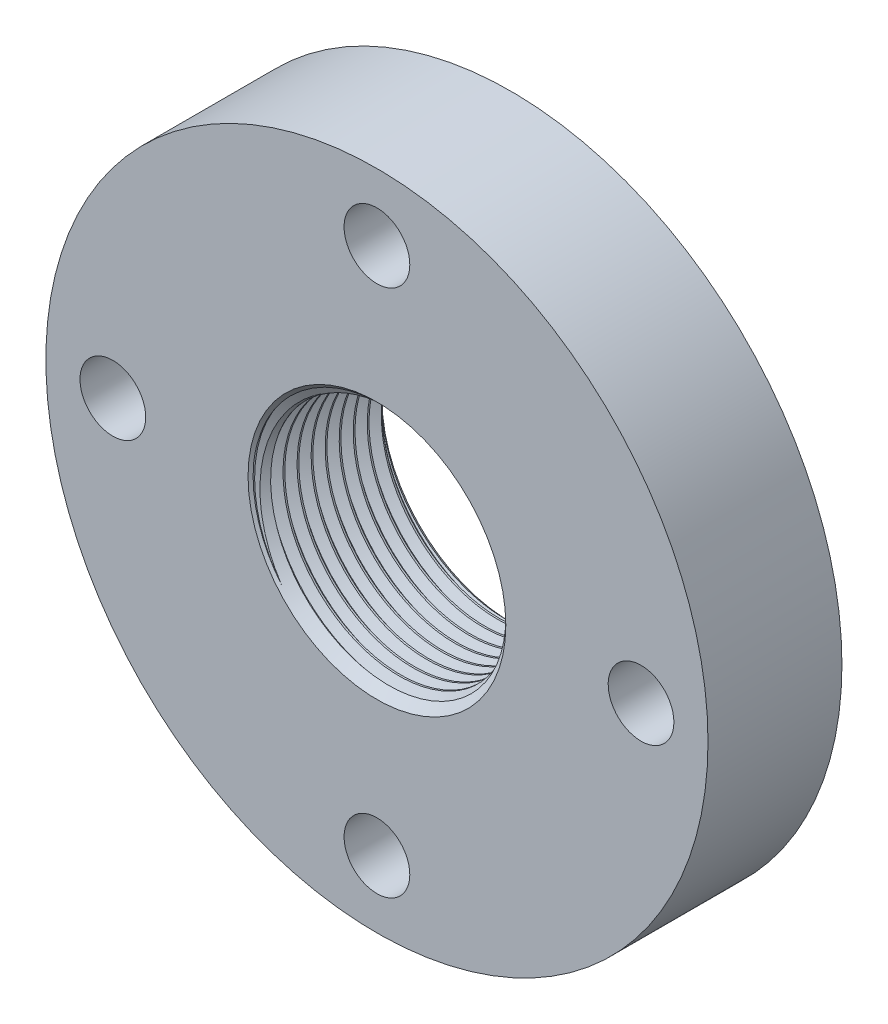
SolidWorks part; units mm, degrees
ref_plane "Front" through (0, 0, 0) normal (0, 0, 1) x (1, 0, 0)
ref_plane "Top" through (0, 0, 0) normal (0, 1, 0) x (1, 0, 0)
ref_plane "Right" through (0, 0, 0) normal (1, 0, 0) x (0, 0, -1)
sketch "Sketch1" plane through (0, 0, 0) normal (0, 0, 1) x (1, 0, 0)
  line L0 (0, 0) -> (0, 26.543) construction
  circle A0 centre (0, 0) radius 33.274
  circle A1 centre (0, 0) radius 12.7 construction
  circle A2 centre (0, 0) radius 26.543 construction
  circle A3 centre (0, 26.543) radius 3.302 construction
  circle A4 centre (0, 0) radius 12.954 construction
  dimension "E" = 66.548
  dimension "G" = 53.086
  dimension "Thread-Dia" = 25.4
  dimension "Mounting-Hole" = 6.604
  dimension "D1" = 25.908
extrude "Boss-Extrude1" add sketch "Sketch1" along normal blind 13.462
sketch "Sketch2" plane through (0, 0, 0) normal (0, 0, 1) x (1, 0, 0)
  circle A0 centre (0, 0) radius 12.7 construction
  circle A1 centre (0, 0) radius 12.7
extrude "Boss-Extrude2" add sketch "Sketch2" along normal up to surface (13.462 mm away) separate body up to face at (33.274, 0, 13.462)
sketch "Sketch3" plane through (0, 0, 0) normal (1, 0, 0) x (0, 0, -1)
  line L0 (0, 0) -> (1.4111, 0) construction
  line L1 (0, 12.7) -> (1.2347, 12.7)
  line L2 (1.2347, 12.7) -> (0.7056, 11.7835)
  line L3 (0.7056, 11.7835) -> (0.5292, 11.7835)
  line L4 (0.5292, 11.7835) -> (0, 12.7)
  line L5 (0.6174, 12.7) -> (0.6174, 11.7835) construction
  line L6 (0.2646, 12.2417) -> (0.9701, 12.2417) construction
  dimension "Pitch" = 1.4111
  dimension "D1" = 0.7056
  dimension "D2" = 0.1764
  dimension "D3" = 60
sketch "Sketch4" plane through (0, 0, 0) normal (0, 0, 1) x (1, 0, 0)
  circle A0 centre (0, 0) radius 12.7 construction
  circle A1 centre (0, 0) radius 12.7
curve "Helix/Spiral1" pitch 1.4111 height 16.637 radius 12.7 centre (0, 0, 0) axis (0, 0, 1) start towards (0.7071, 0.7071, 0) parameters "Lead"=1.4111
sketch "Sketch5" plane through (0, 0, 0) normal (0, 0, 1) x (1, 0, 0)
  circle A0 centre (0, 26.543) radius 3.302 construction
  circle A1 centre (0, 26.543) radius 3.302
extrude "Cut-Extrude1" cut sketch "Sketch5" along normal up to surface (13.462 mm away) up to face at (33.274, 0, 13.462)
ref_axis "Axis1" through (0, 0, 13.462) along (0, 0, -1)
pattern_circular "CirPattern1" count 4 over 360 about axis through (0, 0, 13.462) along (0, 0, -1) of "Cut-Extrude1"
sweep "Cut-Sweep1" cut profiles "Sketch3" path "Helix/Spiral1" align with end faces yes
combine bodies "Combine1" operation type subtract main body 113 bodies to subtract 111
ref_plane "Plane1" through (0, 0, 6.731) normal (0, 0, -1) x (-1, 0, 0)
sketch "Sketch6" plane through (0, 0, 0) normal (0, 0, 1) x (1, 0, 0)
  circle A0 centre (0, 0) radius 12.954 construction
  circle A1 centre (0, 0) radius 12.954
extrude "Cut-Extrude2" cut sketch "Sketch6" along normal blind 2.54 draft 45
mirror "Mirror1" about plane through (0, 0, 6.731) normal (0, 0, -1) of "Cut-Extrude2"
sketch "Sketch7" plane through (0, 0, 0) normal (0, 0, 1) x (1, 0, 0)
  circle A0 centre (0, 0) radius 26.543 construction
  circle A1 centre (0, 0) radius 26.543 construction
equation "\"D1@Sketch3\" = \"Pitch@Sketch3\"/2"
equation "\"D1@Sketch1\" = \"Thread-Dia@Sketch1\"*1.02"
equation "\"D2@Sketch3\" = \"Pitch@Sketch3\"/8"
equation "\"D3@Helix/Spiral1\" = \"F@Boss-Extrude1\"+.125"
